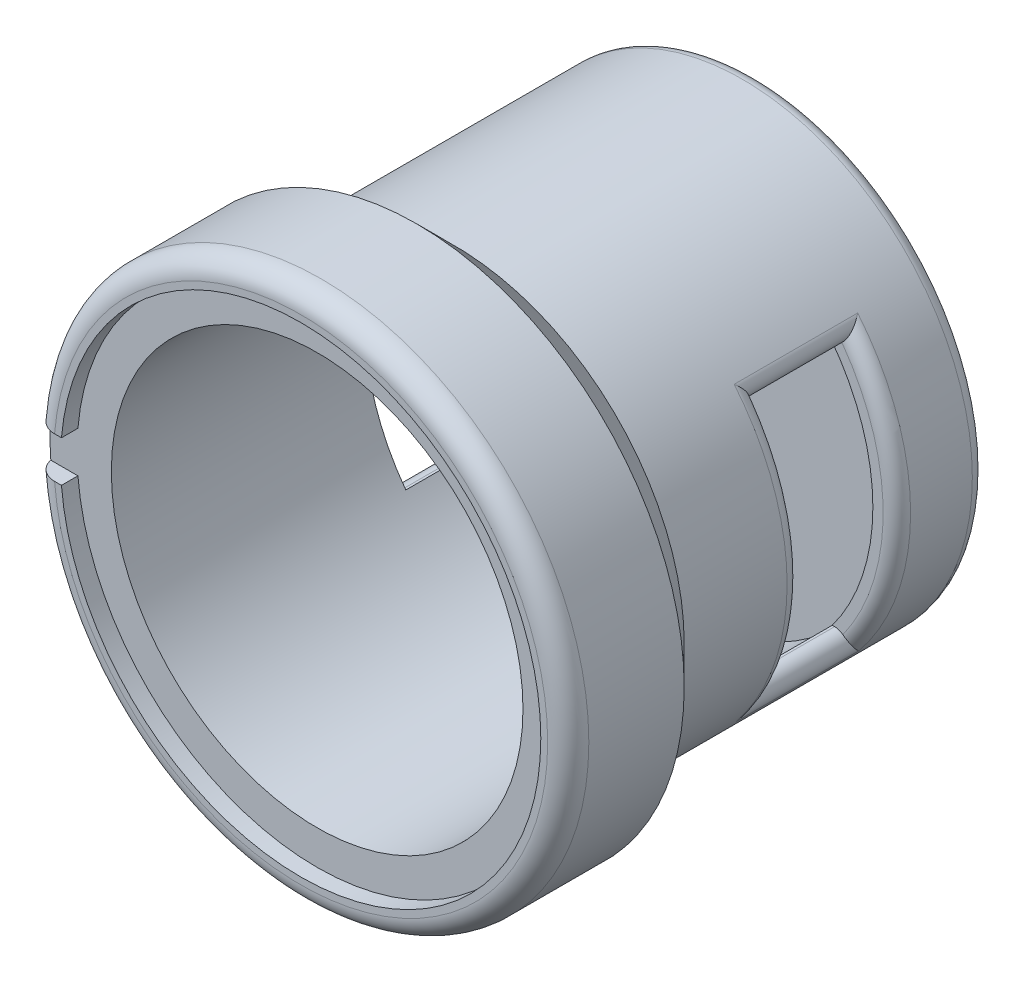
SolidWorks part; units mm, degrees
ref_plane "前视基准面" through (0, 0, 0) normal (0, 0, 1) x (1, 0, 0)
ref_plane "上视基准面" through (0, 0, 0) normal (0, 1, 0) x (1, 0, 0)
ref_plane "右视基准面" through (0, 0, 0) normal (1, 0, 0) x (0, 0, -1)
sketch "草图1" plane through (0, 0, 0) normal (0, 0, 1) x (1, 0, 0)
  circle A0 centre (0, 0) radius 16.75
  dimension "D1" = 33.5
extrude "凸台-拉伸1" add sketch "草图1" along normal blind 5
sketch "草图6" plane through (0, 0, 5) normal (0, 0, 1) x (1, 0, 0)
  circle A0 centre (0, 0) radius 15
  circle A1 centre (0, 0) radius 16.75
  circle A2 centre (0, 0) radius 16.75
  dimension "D1" = 0
extrude "凸台-拉伸5" add sketch "草图6" along normal blind 20
sketch "草图7" plane through (0, 0, 25) normal (0, 0, 1) x (1, 0, 0)
  circle A0 centre (0, 0) radius 15
  circle A1 centre (0, 0) radius 19.5
extrude "凸台-拉伸6" add sketch "草图7" along normal blind 7
sketch "草图8" plane through (0, 0, 32) normal (0, 0, 1) x (1, 0, 0)
  circle A0 centre (0, 0) radius 17.5
  circle A1 centre (0, 0) radius 19.5
extrude "凸台-拉伸7" add sketch "草图8" along normal blind 1.2
fillet "圆角3" radius 1.5 1 edges at (19.5, 0, 33.2)
chamfer "倒角1" distance 3 angle 45 1 edges at (16.75, 0, 25)
sketch "草图9" plane through (0, 0, 0) normal (1, 0, 0) x (0, 0, -1)
  line L0 (0, -16.75) -> (0, 16.75) construction
  line L1 (-13.5, -8.9466) -> (-6.5, -8.9466)
  line L2 (-13.5, -8.9466) -> (-13.5, 9.0534)
  line L3 (-13.5, 9.0534) -> (-6.5, 9.0534)
  line L4 (-6.5, -8.9466) -> (-6.5, 9.0534)
  line L5 (-13.5, -8.9466) -> (-6.5, 9.0534) construction
  line L6 (-13.5, 9.0534) -> (-6.5, -8.9466) construction
  point P0 (-10, 0.0534)
  dimension "D1" = 18
  dimension "D2" = 7
  dimension "D3" = 10
extrude "切除-拉伸2" cut sketch "草图9" along normal blind 20 from offset 8
extrude "切除-拉伸3" cut sketch "草图9<2>" against normal blind 20 from offset 8 offset against normal yes
sketch "草图9<2>" plane through (0, 0, 0) normal (1, 0, 0) x (0, 0, -1) same geometry as "草图9"
sketch "草图10" plane through (0, 0, 5) normal (0, 0, 1) x (1, 0, 0)
  line L1 (-12.5, -3.25) -> (-9.5, -3.25)
  line L2 (-14.5, -1.25) -> (-14.5, 1.25)
  line L3 (-12.5, 3.25) -> (-9.5, 3.25)
  line L4 (-7.5, -1.25) -> (-7.5, 1.25)
  line L5 (-14.5, -3.25) -> (-7.5, 3.25) construction
  line L6 (-14.5, 3.25) -> (-7.5, -3.25) construction
  arc A0 (-12.5, -3.25) -> (-14.5, -1.25) centre (-12.5, -1.25) cw
  arc A1 (-9.5, -3.25) -> (-7.5, -1.25) centre (-9.5, -1.25) ccw
  arc A2 (-9.5, 3.25) -> (-7.5, 1.25) centre (-9.5, 1.25) cw
  arc A3 (-14.5, 1.25) -> (-12.5, 3.25) centre (-12.5, 1.25) cw
  point P0 (-11, 0)
  dimension "D3" = 2
  dimension "D4" = 11
  dimension "D1" = 7
  dimension "D2" = 6.5
extrude "切除-拉伸4" cut sketch "草图10" against normal up to next
fillet "圆角4" radius 1 17 edges at (-8.0858, 2.6642, 0) (-11, 3.25, 0) (-13.9142, 2.6642, 0) (-14.5, 0, 0) (-13.9142, -2.6642, 0) (-11, -3.25, 0) (-8.0858, -2.6642, 0) (16.7499, 0.0634, 13.5) (14.1606, -8.9466, 10) (14.0925, 9.0534, 10) (16.7499, 0.0634, 6.5) (-16.7499, 0.0634, 13.5) (-14.1606, -8.9466, 10) (-16.7499, 0.0634, 6.5) (-14.0925, 9.0534, 10) (-7.5, 0, 0) (16.75, 0, 0)
sketch "草图11" plane through (0, 0, 32) normal (0, 0, 1) x (1, 0, 0)
  line L1 (-12.235, -1.5) -> (-21.2512, -1.5)
  line L2 (-12.235, -1.5) -> (-12.235, 1.5)
  line L3 (-12.235, 1.5) -> (-21.2512, 1.5)
  line L4 (-21.2512, -1.5) -> (-21.2512, 1.5)
  line L5 (-12.235, -1.5) -> (-21.2512, 1.5) construction
  line L6 (-12.235, 1.5) -> (-21.2512, -1.5) construction
  point P0 (-16.7431, 0)
  point P5 (0, 0)
  dimension "D1" = 3
extrude "切除-拉伸5" cut sketch "草图11" along normal up to next
